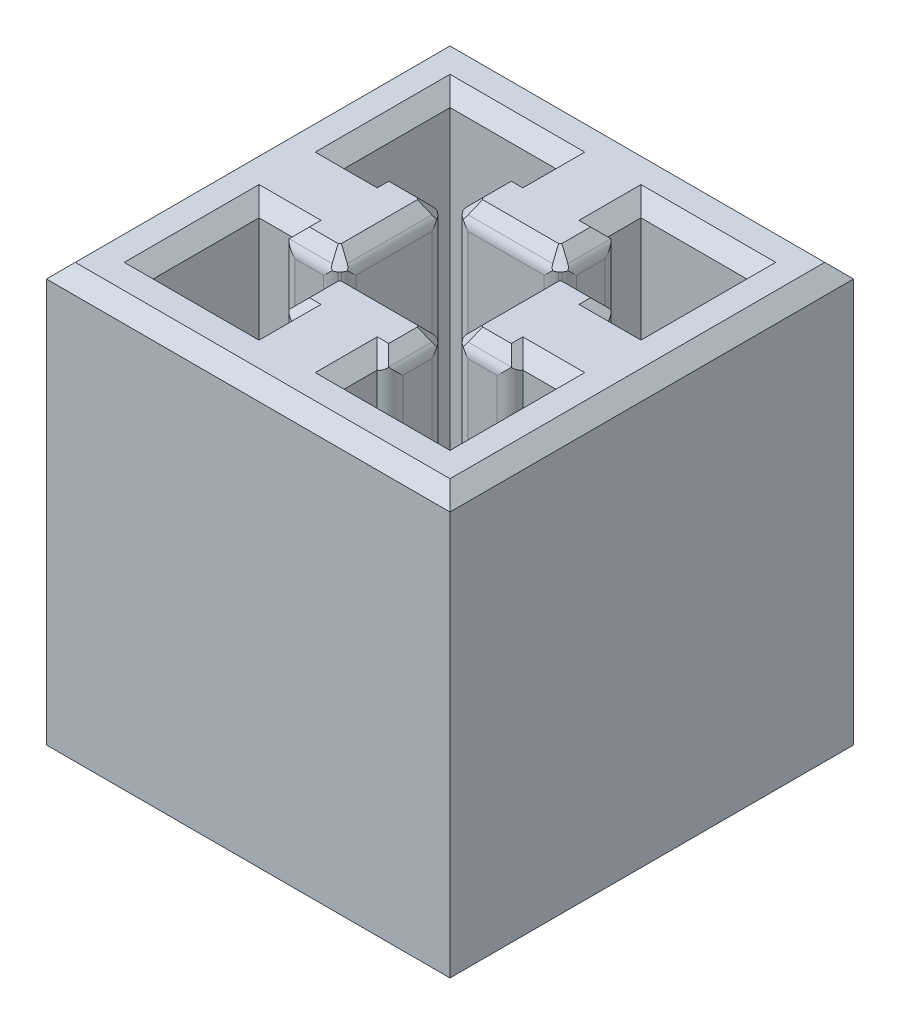
SolidWorks part; units mm, degrees
ref_plane "前视基准面" through (0, 0, 0) normal (0, 0, 1) x (1, 0, 0)
ref_plane "上视基准面" through (0, 0, 0) normal (0, 1, 0) x (1, 0, 0)
ref_plane "右视基准面" through (0, 0, 0) normal (1, 0, 0) x (0, 0, -1)
other "Configuration Table"
sketch "草图1" plane through (0, 0, 0) normal (0, 1, 0) x (1, 0, 0)
  line L0 (-10, 0) -> (10, 0) construction
  line L1 (-10, -10) -> (10, -10)
  line L2 (-10, -10) -> (-10, 10)
  line L3 (-10, 10) -> (10, 10)
  line L4 (10, -10) -> (10, 10)
  line L5 (-10, -10) -> (10, 10) construction
  line L6 (-10, 10) -> (10, -10) construction
  line L7 (0, 10) -> (0, -10) construction
  line L8 (-3.15, 10) -> (-3.15, 8.2)
  line L9 (-3.15, 8.2) -> (-3.95, 8.2)
  line L10 (-3.95, 8.2) -> (-3.95, 9.2)
  line L11 (-3.95, 9.2) -> (-5.6343, 9.2)
  line L12 (-5.6343, 9.2) -> (-5.6343, 6.2)
  line L13 (-5.6343, 6.2) -> (-3.1343, 3.7)
  line L14 (-3.1343, 3.7) -> (3.1343, 3.7)
  line L15 (5.6343, 6.2) -> (3.1343, 3.7)
  line L16 (5.6343, 9.2) -> (5.6343, 6.2)
  line L17 (3.95, 9.2) -> (5.6343, 9.2)
  line L18 (3.95, 8.2) -> (3.95, 9.2)
  line L19 (3.15, 8.2) -> (3.95, 8.2)
  line L20 (3.15, 10) -> (3.15, 8.2)
  line L21 (3.15, -10) -> (3.15, -8.2)
  line L22 (3.15, -8.2) -> (3.95, -8.2)
  line L23 (3.95, -8.2) -> (3.95, -9.2)
  line L24 (5.6343, -9.2) -> (5.6343, -6.2)
  line L25 (5.6343, -6.2) -> (3.1343, -3.7)
  line L26 (-3.1343, -3.7) -> (3.1343, -3.7)
  line L27 (-5.6343, -6.2) -> (-3.1343, -3.7)
  line L28 (-5.6343, -9.2) -> (-5.6343, -6.2)
  line L29 (-3.95, -9.2) -> (-5.6343, -9.2)
  line L30 (-3.95, -8.2) -> (-3.95, -9.2)
  line L31 (-3.15, -8.2) -> (-3.95, -8.2)
  line L32 (-3.15, -10) -> (-3.15, -8.2)
  line L33 (-6.2, 5.6343) -> (-3.7, 3.1343)
  line L34 (-9.2, 5.6343) -> (-6.2, 5.6343)
  line L35 (-9.2, 3.95) -> (-9.2, 5.6343)
  line L36 (-8.2, 3.95) -> (-9.2, 3.95)
  line L37 (-8.2, 3.15) -> (-8.2, 3.95)
  line L38 (-10, 3.15) -> (-8.2, 3.15)
  line L39 (-3.7, 3.1343) -> (-3.7, -3.1343)
  line L40 (-10, -3.15) -> (-8.2, -3.15)
  line L41 (-8.2, -3.15) -> (-8.2, -3.95)
  line L42 (-8.2, -3.95) -> (-9.2, -3.95)
  line L43 (-9.2, -3.95) -> (-9.2, -5.6343)
  line L44 (-9.2, -5.6343) -> (-6.2, -5.6343)
  line L45 (-6.2, -5.6343) -> (-3.7, -3.1343)
  line L46 (10, -3.15) -> (8.2, -3.15)
  line L47 (8.2, -3.15) -> (8.2, -3.95)
  line L48 (8.2, -3.95) -> (9.2, -3.95)
  line L49 (9.2, -3.95) -> (9.2, -5.6343)
  line L50 (9.2, -5.6343) -> (6.2, -5.6343)
  line L51 (6.2, -5.6343) -> (3.7, -3.1343)
  line L52 (3.7, -3.1343) -> (3.7, 3.1343)
  line L53 (6.2, 5.6343) -> (3.7, 3.1343)
  line L54 (9.2, 5.6343) -> (6.2, 5.6343)
  line L55 (9.2, 3.95) -> (9.2, 5.6343)
  line L56 (8.2, 3.95) -> (9.2, 3.95)
  line L57 (8.2, 3.15) -> (8.2, 3.95)
  line L58 (10, 3.15) -> (8.2, 3.15)
  line L59 (3.95, -9.2) -> (5.6343, -9.2)
  line L60 (8.2, -3.95) -> (4.5157, -3.95)
  line L61 (-14, -14) -> (14, -14)
  line L62 (-14, -14) -> (-14, 14)
  line L63 (-14, 14) -> (14, 14)
  line L64 (14, -14) -> (14, 14)
  line L65 (-14, -14) -> (14, 14) construction
  line L66 (-14, 14) -> (14, -14) construction
  line L67 (8.2, 3.95) -> (4.5157, 3.95)
  line L68 (3.95, -8.2) -> (3.95, -4.5157)
  line L69 (-3.95, -8.2) -> (-3.95, -4.5157)
  line L70 (-8.2, -3.95) -> (-4.5157, -3.95)
  line L71 (-8.2, 3.95) -> (-4.5157, 3.95)
  line L72 (-3.95, 8.2) -> (-3.95, 4.5157)
  line L73 (3.95, 8.2) -> (3.95, 4.5157)
  line L74 (0, 0) -> (4.5157, -3.95) construction
  point P0 (0, 0)
  point P18 (0, 3.7)
  point P67 (0, 0)
  point P69 (0, 0)
  point P75 (-3.95, 4.5157)
  point P77 (0, 0)
  point P82 (0, 0)
  point P87 (0, 0)
  dimension "D1" = 20
  dimension "D2" = 20
  dimension "D3" = 6.85
  dimension "D4" = 1.8
  dimension "D5" = 0.8
  dimension "D6" = 1
  dimension "D7" = 6.3
  dimension "D8" = 0.4
  dimension "D9" = 3
  dimension "D10" = 28
  dimension "D11" = 4
  dimension "D12" = 5.9995
sketch "草图2" plane through (0, 0, 0) normal (0, 1, 0) x (1, 0, 0)
  line L0 (-10.3, 2.95) -> (-8, 2.95)
  line L1 (-8, 2.95) -> (-8, 3.75)
  line L2 (-8, 3.75) -> (-4.5985, 3.75)
  line L3 (-4.5985, 3.75) -> (-3.9, 3.0515)
  line L4 (-3.7, 3.1343) -> (-3.7, -3.1343) construction
  line L5 (-6.2, 5.6343) -> (-3.7, 3.1343) construction
  line L6 (-6.2, -5.6343) -> (-3.7, -3.1343) construction
  line L7 (-8.2, -3.95) -> (-4.5157, -3.95) construction
  line L8 (10.3, -10.3) -> (10.3, 10.3)
  line L9 (-10.3, -10.3) -> (10.3, -10.3)
  line L10 (10.3, 10.3) -> (-10.3, 10.3)
  line L11 (-10.3, 10.3) -> (-10.3, -10.3)
  line L12 (10.3, -10.3) -> (10.3, 10.3)
  line L13 (-10.3, -10.3) -> (10.3, -10.3)
  line L14 (10.3, 10.3) -> (-10.3, 10.3)
  line L15 (-10.3, 10.3) -> (-10.3, -10.3)
  line L16 (-8.2, -3.15) -> (-8.2, -3.95) construction
  line L17 (-10, -3.15) -> (-8.2, -3.15) construction
  line L18 (-10, 3.15) -> (-8.2, 3.15) construction
  line L19 (-8.2, 3.15) -> (-8.2, 3.95) construction
  line L20 (-8.2, 3.95) -> (-4.5157, 3.95) construction
  line L21 (-3.9, 3.0515) -> (-3.9, -3.0515)
  line L22 (-4.5985, -3.75) -> (-3.9, -3.0515)
  line L23 (-8, -3.75) -> (-4.5985, -3.75)
  line L24 (-8, -2.95) -> (-8, -3.75)
  line L25 (-10.3, -2.95) -> (-8, -2.95)
  line L26 (-10, 2.95) -> (-8, 2.95) construction
  line L27 (-10, -2.95) -> (-8, -2.95) construction
  line L28 (2.95, 10.3) -> (2.95, 8)
  line L29 (-2.95, 10.3) -> (-2.95, 8)
  line L30 (-3.75, 8) -> (-3.75, 4.5985)
  line L31 (-2.95, 8) -> (-3.75, 8)
  line L32 (2.95, 8) -> (3.75, 8)
  line L33 (3.75, 8) -> (3.75, 4.5985)
  line L34 (3.75, 4.5985) -> (3.0515, 3.9)
  line L35 (3.0515, 3.9) -> (-3.0515, 3.9)
  line L36 (-3.75, 4.5985) -> (-3.0515, 3.9)
  line L37 (10.3, -2.95) -> (8, -2.95)
  line L38 (10.3, 2.95) -> (8, 2.95)
  line L39 (8, 3.75) -> (4.5985, 3.75)
  line L40 (8, 2.95) -> (8, 3.75)
  line L41 (8, -2.95) -> (8, -3.75)
  line L42 (8, -3.75) -> (4.5985, -3.75)
  line L43 (4.5985, -3.75) -> (3.9, -3.0515)
  line L44 (3.9, -3.0515) -> (3.9, 3.0515)
  line L45 (4.5985, 3.75) -> (3.9, 3.0515)
  line L46 (-2.95, -10.3) -> (-2.95, -8)
  line L47 (2.95, -10.3) -> (2.95, -8)
  line L48 (3.75, -8) -> (3.75, -4.5985)
  line L49 (2.95, -8) -> (3.75, -8)
  line L50 (-2.95, -8) -> (-3.75, -8)
  line L51 (-3.75, -8) -> (-3.75, -4.5985)
  line L52 (-3.75, -4.5985) -> (-3.0515, -3.9)
  line L53 (-3.0515, -3.9) -> (3.0515, -3.9)
  line L54 (3.75, -4.5985) -> (3.0515, -3.9)
  line L55 (0, 0) -> (-3.9, 3.0515) construction
  line L56 (-14, -14) -> (14, -14) construction
  line L57 (14, -14) -> (14, 14) construction
  line L58 (-14, 14) -> (14, 14) construction
  line L59 (-14, -14) -> (-14, 14) construction
  line L60 (-14, -14) -> (14, -14)
  line L61 (14, -14) -> (14, 14)
  line L62 (-14, 14) -> (14, 14)
  line L63 (-14, -14) -> (-14, 14)
  line L75 (-3.7, 3.1343) -> (-3.7, -3.1343) construction
  line L76 (-4.5157, 3.95) -> (-3.7, 3.1343) construction
  line L77 (-4.5157, -3.95) -> (-3.7, -3.1343) construction
  line L78 (-8.2, -3.95) -> (-4.5157, -3.95) construction
  line L79 (-8.2, -3.15) -> (-8.2, -3.95) construction
  line L80 (-10, -3.15) -> (-8.2, -3.15) construction
  line L81 (-10, 3.15) -> (-8.2, 3.15) construction
  line L82 (-8.2, 3.15) -> (-8.2, 3.95) construction
  line L83 (-8.2, 3.95) -> (-4.5157, 3.95) construction
  point P3 (0, 0)
  dimension "D2" = 0.2
  dimension "D3" = 4
  dimension "D4" = 4.9519
  dimension "D1" = 0.3
extrude "凸台-拉伸2" add sketch "草图2" along normal blind 30 contours L15 L25 L24 L23 L22 L21 L3 L2 L1 L0 | L30 L36 L35 L34 L33 L32 L28 L14 L29 L31 | L39 L45 L44 L43 L42 L41 L37 L12 L38 L40 | L48 L54 L53 L52 L51 L50 L46 L13 L47 L49 | L63 L60 L61 L62 L15 L14 L12 L13
chamfer "倒角1" distance 1 angle 45 96 edges at (0, 0, -14) (0, 30, -14) (14, 0, 0) (14, 30, 0) (0, 0, 14) (0, 30, 14) (-14, 0, 0) (-14, 30, 0) (-8, 0, -3.35) (-8, 30, -3.35) (-6.2993, 0, -3.75) (-6.2993, 30, -3.75) (-3.9, 0, 0) (-3.9, 30, 0) (-6.2993, 0, 3.75) (-6.2993, 30, 3.75) (-8, 0, 3.35) (-8, 30, 3.35) (-9.15, 0, 2.95) (-9.15, 30, 2.95) (-10.3, 0, 6.625) (-10.3, 30, 6.625) (-6.625, 0, 10.3) (-6.625, 30, 10.3) (-2.95, 0, 9.15) (-2.95, 30, 9.15) (-3.35, 0, 8) (-3.35, 30, 8) (-3.75, 0, 6.2993) (-3.75, 30, 6.2993) (0, 0, 3.9) (0, 30, 3.9) (3.75, 0, 6.2993) (3.75, 30, 6.2993) (3.35, 0, 8) (3.35, 30, 8) (2.95, 0, 9.15) (2.95, 30, 9.15) (6.625, 0, 10.3) (6.625, 30, 10.3) (10.3, 0, 6.625) (10.3, 30, 6.625) (9.15, 0, 2.95) (9.15, 30, 2.95) (8, 0, 3.35) (8, 30, 3.35) (6.2993, 0, 3.75) (6.2993, 30, 3.75) (3.9, 0, 0) (3.9, 30, 0) (6.2993, 0, -3.75) (6.2993, 30, -3.75) (8, 0, -3.35) (8, 30, -3.35) (9.15, 0, -2.95) (9.15, 30, -2.95) (10.3, 0, -6.625) (10.3, 30, -6.625) (6.625, 0, -10.3) (6.625, 30, -10.3) (2.95, 0, -9.15) (2.95, 30, -9.15) (3.35, 0, -8) (3.35, 30, -8) (3.75, 0, -6.2993) (3.75, 30, -6.2993) (0, 0, -3.9) (0, 30, -3.9) (-3.75, 0, -6.2993) (-3.75, 30, -6.2993) (-3.35, 0, -8) (-3.35, 30, -8) (-2.95, 0, -9.15) (-2.95, 30, -9.15) (-6.625, 0, -10.3) (-6.625, 30, -10.3) (-10.3, 0, -6.625) (-10.3, 30, -6.625) (-9.15, 0, -2.95) (-9.15, 30, -2.95) (-4.2493, 0, -3.4007) (-4.2493, 30, -3.4007) (-4.2493, 0, 3.4007) (-4.2493, 30, 3.4007) (-3.4007, 0, 4.2493) (-3.4007, 30, 4.2493) (3.4007, 0, 4.2493) (3.4007, 30, 4.2493) (4.2493, 0, 3.4007) (4.2493, 30, 3.4007) (4.2493, 0, -3.4007) (4.2493, 30, -3.4007) (3.4007, 0, -4.2493) (3.4007, 30, -4.2493) (-3.4007, 0, -4.2493) (-3.4007, 30, -4.2493)
fillet "圆角3" radius 1 48 edges at (3.75, 1, 6.2993) (3.75, 15, 8) (3.75, 29, 6.2993) (3.75, 15, 4.5985) (6.2993, 1, -3.75) (8, 15, -3.75) (6.2993, 29, -3.75) (4.5985, 15, -3.75) (6.2993, 1, 3.75) (4.5985, 15, 3.75) (6.2993, 29, 3.75) (8, 15, 3.75) (3.9, 1, 0) (3.9, 15, -3.0515) (3.9, 29, 0) (3.9, 15, 3.0515) (0, 1, 3.9) (3.0515, 15, 3.9) (0, 29, 3.9) (-3.0515, 15, 3.9) (-3.75, 1, 6.2993) (-3.75, 15, 4.5985) (-3.75, 29, 6.2993) (-3.75, 15, 8) (3.75, 1, -6.2993) (3.75, 15, -4.5985) (3.75, 29, -6.2993) (3.75, 15, -8) (-3.75, 1, -6.2993) (-3.75, 15, -8) (-3.75, 29, -6.2993) (-3.75, 15, -4.5985) (0, 1, -3.9) (-3.0515, 15, -3.9) (0, 29, -3.9) (3.0515, 15, -3.9) (-6.2993, 1, -3.75) (-4.5985, 15, -3.75) (-6.2993, 29, -3.75) (-8, 15, -3.75) (-3.9, 1, 0) (-3.9, 15, 3.0515) (-3.9, 29, 0) (-3.9, 15, -3.0515) (-6.2993, 1, 3.75) (-8, 15, 3.75) (-6.2993, 29, 3.75) (-4.5985, 15, 3.75)
